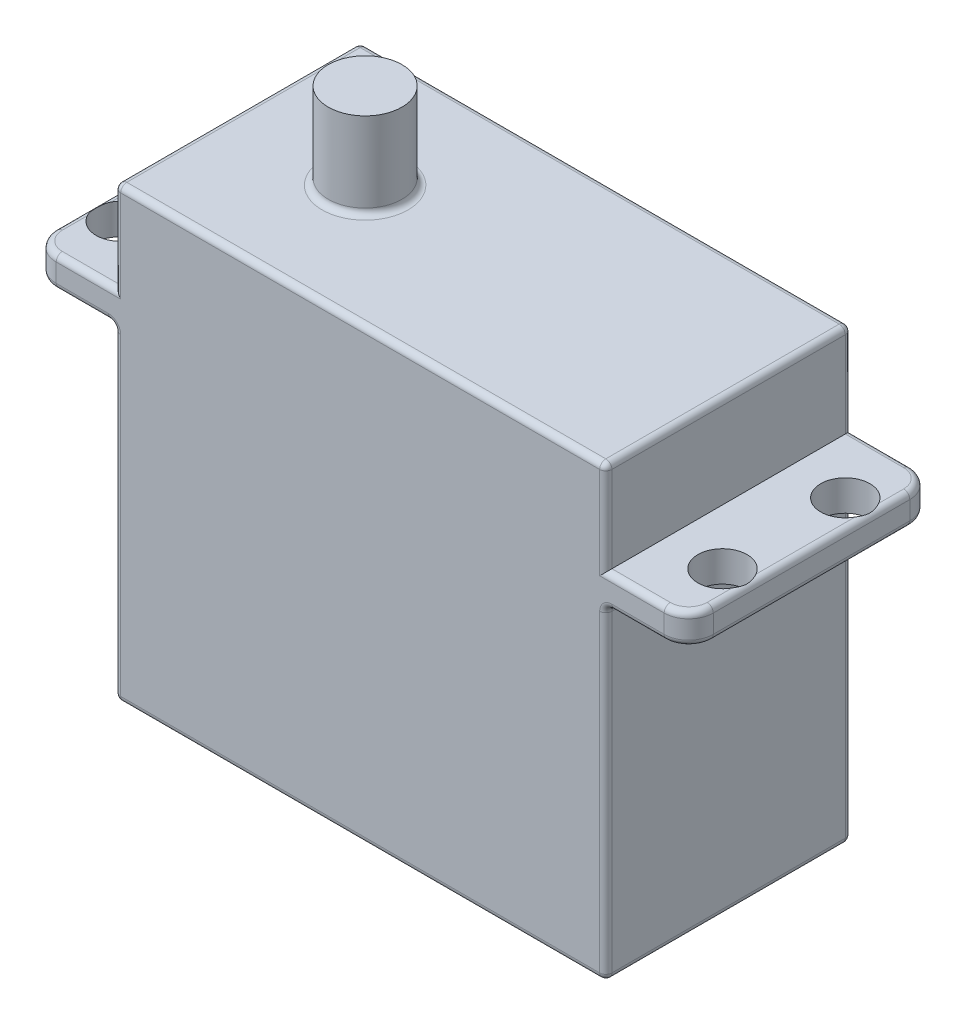
SolidWorks part; units mm, degrees
material "ABS"
ref_plane "Спереди" through (0, 0, 0) normal (0, 0, 1) x (1, 0, 0)
ref_plane "Сверху" through (0, 0, 0) normal (0, 1, 0) x (1, 0, 0)
ref_plane "Справа" through (0, 0, 0) normal (1, 0, 0) x (0, 0, -1)
other "Configuration Table"
sketch "Эскиз1" plane through (0, 0, 0) normal (0, 1, 0) x (1, 0, 0)
  line L1 (0, 0) -> (40, 0)
  line L2 (0, 0) -> (0, 20)
  line L3 (0, 20) -> (40, 20)
  line L4 (40, 0) -> (40, 20)
  dimension "D1" = 40
  dimension "D2" = 20
extrude "Бобышка-Вытянуть1" add sketch "Эскиз1" along normal blind 36.5
ref_plane "Плоскость1" through (0, 26.5, 0) normal (0, -1, 0) x (-1, 0, 0)
sketch "Эскиз2" plane through (0, 26.5, 0) normal (0, -1, 0) x (-1, 0, 0)
  line L0 (-40, 20) -> (0, 20) construction
  line L1 (-44.75, 20) -> (4.75, 20)
  line L3 (-44.75, 0) -> (4.75, 0)
  line L5 (0, 0) -> (-40, 0) construction
  line L6 (-47.5253, 10) -> (35.1632, 10) construction
  line L7 (-20, 25.463) -> (-20, -9.827) construction
  line L10 (6.75, 4.0318) -> (6.75, 2)
  line L11 (-46.75, 18) -> (-46.75, 2)
  line L12 (6.75, 18) -> (6.75, 4.0318)
  arc A4 (4.75, 0) -> (6.75, 2) centre (4.75, 2) ccw
  arc A5 (4.75, 20) -> (6.75, 18) centre (4.75, 18) cw
  arc A6 (-46.75, 18) -> (-44.75, 20) centre (-44.75, 18) cw
  arc A7 (-46.75, 2) -> (-44.75, 0) centre (-44.75, 2) ccw
  circle A8 centre (-44.5, 15) radius 2
  circle A9 centre (-44.5, 5) radius 2
  circle A10 centre (4.5, 15) radius 2
  circle A11 centre (4.5, 5) radius 2
  point P6 (-20, 20)
  point P7 (-20, 20)
  point P26 (6.75, 0)
  point P33 (-46.75, 0)
  dimension "D5" = 2
  dimension "D6" = 4
  dimension "D7" = 5
  dimension "D8" = 24.5
  dimension "D9" = 5
  dimension "D10" = 5
  dimension "D11" = 5
  dimension "D12" = 24.5
extrude "Бобышка-Вытянуть2" add sketch "Эскиз2" against normal blind 2.5
sketch "Эскиз3" plane through (0, 36.5, 0) normal (0, 1, 0) x (1, 0, 0)
  line L0 (0, 20) -> (0, 0) construction
  line L1 (0, 0) -> (40, 0) construction
  line L2 (40, 20) -> (0, 20) construction
  line L3 (40, 0) -> (40, 20) construction
  line L4 (403.3948, 23.841) -> (458.8948, 23.841) construction
  circle A0 centre (10.4, 10) radius 3
  dimension "D2" = 6
  dimension "D1" = 10.4
  dimension "D3" = 20
  dimension "D4" = 10
  dimension "D5" = 29.6
  dimension "D6" = 55.5
extrude "Бобышка-Вытянуть3" add sketch "Эскиз3" along normal blind 7
fillet "Скругление5" radius 0.5 39 edges at (-6.1642, 29, -19.4142) (-6.1642, 26.5, -19.4142) (46.1642, 26.5, -19.4142) (46.1642, 29, -19.4142) (46.1642, 29, -0.5858) (46.1642, 26.5, -0.5858) (-6.75, 26.5, -10) (-6.1642, 26.5, -0.5858) (-6.75, 29, -10) (-6.1642, 29, -0.5858) (40, 36.5, -10) (0, 36.5, -10) (10.4, 36.5, -13) (40, 26.5, -10) (20, 36.5, -20) (0, 32.75, -20) (-2.375, 29, -20) (-2.375, 26.5, -20) (40, 13.25, -20) (42.375, 26.5, -20) (42.375, 29, -20) (40, 32.75, -20) (0, 13.25, -20) (0, 26.5, -10) (20, 36.5, 0) (40, 32.75, 0) (42.375, 29, 0) (42.375, 26.5, 0) (40, 13.25, 0) (0, 13.25, 0) (-2.375, 26.5, 0) (-2.375, 29, 0) (0, 32.75, 0) (20, 0, 0) (40, 0, -10) (20, 0, -20) (0, 0, -10) (46.75, 29, -10) (46.75, 26.5, -10)
